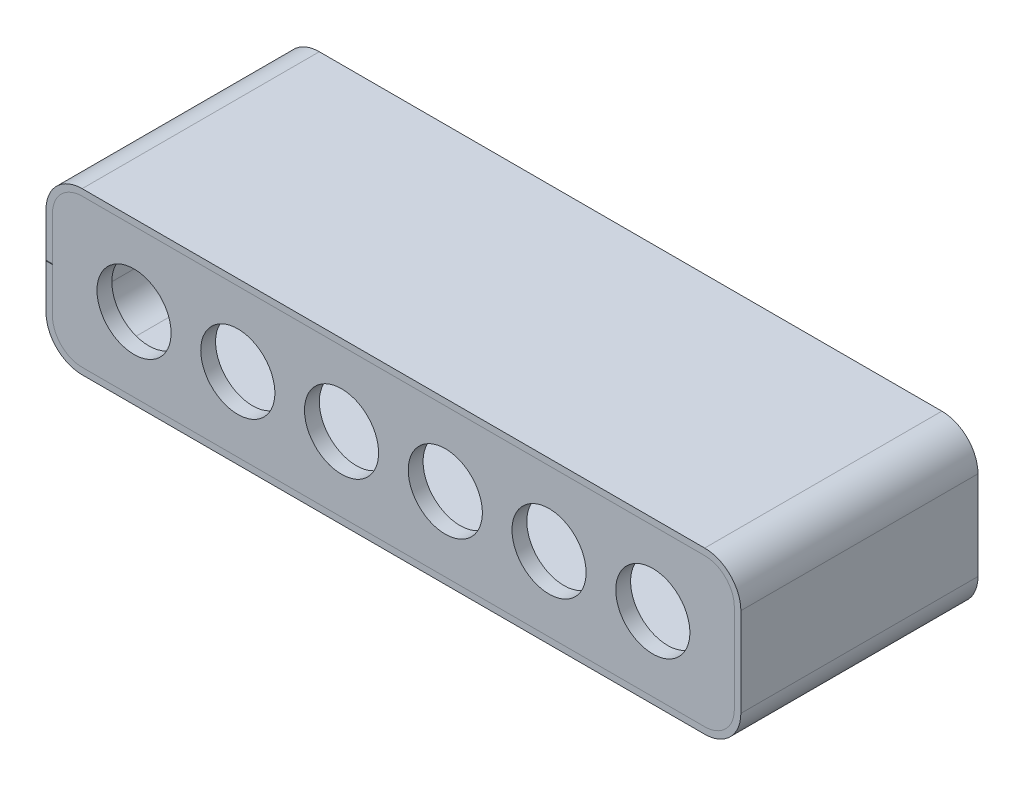
SolidWorks part; units mm, degrees
material "Acrylic (Medium-high impact)"
ref_plane "Front" through (0, 0, 0) normal (0, 0, 1) x (1, 0, 0)
ref_plane "Top" through (0, 0, 0) normal (0, 1, 0) x (1, 0, 0)
ref_plane "Right" through (0, 0, 0) normal (1, 0, 0) x (0, 0, -1)
sketch "Sketch1" plane through (0, 0, 0) normal (0, 0, 1) x (1, 0, 0)
  line L1 (-146.05, 31.75) -> (146.05, 31.75)
  line L2 (-146.05, 31.75) -> (-146.05, -31.75)
  line L3 (-146.05, -31.75) -> (146.05, -31.75)
  line L4 (146.05, 31.75) -> (146.05, -31.75)
  line L5 (-146.05, 31.75) -> (146.05, -31.75) construction
  line L6 (-146.05, -31.75) -> (146.05, 31.75) construction
  point P0 (0, 0)
  dimension "D1" = 292.1
  dimension "D2" = 63.5
extrude "Boss-Extrude1" add sketch "Sketch1" along normal blind 6.35
fillet "Fillet1" radius 12.7 4 edges at (-146.05, -31.75, 3.175) (146.05, -31.75, 3.175) (146.05, 31.75, 3.175) (-146.05, 31.75, 3.175)
sketch "Sketch3" plane through (0, 0, 0) normal (0, 0, 1) x (1, 0, 0)
  line L0 (133.35, 34.544) -> (-133.35, 34.544)
  line L1 (-148.844, 19.05) -> (-148.844, 0.254)
  line L2 (-133.35, -34.544) -> (133.35, -34.544)
  line L3 (148.844, -19.05) -> (148.844, 19.05)
  line L4 (-133.35, -31.75) -> (133.35, -31.75)
  line L5 (-146.05, 19.05) -> (-146.05, -19.05)
  line L6 (133.35, 31.75) -> (-133.35, 31.75)
  line L7 (146.05, -19.05) -> (146.05, 19.05)
  line L8 (-133.35, -31.75) -> (133.35, -31.75)
  line L9 (-146.05, 19.05) -> (-146.05, 0.254)
  line L10 (133.35, 31.75) -> (-133.35, 31.75)
  line L11 (146.05, -19.05) -> (146.05, 19.05)
  line L12 (-146.05, 0) -> (-148.844, 0)
  line L13 (-146.05, 0.254) -> (-148.844, 0.254)
  line L14 (-146.05, 0) -> (-146.05, -19.05)
  line L15 (-146.05, 19.05) -> (-146.05, -19.05) construction
  line L16 (-148.844, 0) -> (-148.844, -19.05)
  line L17 (-148.844, 19.05) -> (-148.844, -19.05) construction
  line L18 (-146.05, 19.05) -> (-146.05, -19.05) construction
  arc A0 (-133.35, 34.544) -> (-148.844, 19.05) centre (-133.35, 19.05) ccw
  arc A1 (-148.844, -19.05) -> (-133.35, -34.544) centre (-133.35, -19.05) ccw
  arc A2 (133.35, -34.544) -> (148.844, -19.05) centre (133.35, -19.05) ccw
  arc A3 (148.844, 19.05) -> (133.35, 34.544) centre (133.35, 19.05) ccw
  arc A4 (-146.05, -19.05) -> (-133.35, -31.75) centre (-133.35, -19.05) ccw
  arc A5 (-133.35, 31.75) -> (-146.05, 19.05) centre (-133.35, 19.05) ccw
  arc A6 (146.05, 19.05) -> (133.35, 31.75) centre (133.35, 19.05) ccw
  arc A7 (133.35, -31.75) -> (146.05, -19.05) centre (133.35, -19.05) ccw
  arc A8 (-146.05, -19.05) -> (-133.35, -31.75) centre (-133.35, -19.05) ccw
  arc A9 (-133.35, 31.75) -> (-146.05, 19.05) centre (-133.35, 19.05) ccw
  arc A10 (146.05, 19.05) -> (133.35, 31.75) centre (133.35, 19.05) ccw
  arc A11 (133.35, -31.75) -> (146.05, -19.05) centre (133.35, -19.05) ccw
  dimension "D3" = 0.254
  dimension "D1" = 0
  dimension "D2" = 2.794
extrude "Boss-Extrude2" add sketch "Sketch3" along normal blind 101.6 separate body
sketch "Sketch4" plane through (0, 0, 101.6) normal (0, 0, 1) x (1, 0, 0)
  line L4 (-146.05, 19.05) -> (-146.05, -19.05)
  line L5 (-133.35, -31.75) -> (133.35, -31.75)
  line L6 (146.05, -19.05) -> (146.05, 19.05)
  line L7 (133.35, 31.75) -> (-133.35, 31.75)
  line L8 (-146.05, 19.05) -> (-146.05, -19.05)
  line L9 (-133.35, -31.75) -> (133.35, -31.75)
  line L10 (146.05, -19.05) -> (146.05, 19.05)
  line L11 (133.35, 31.75) -> (-133.35, 31.75)
  arc A4 (-146.05, -19.05) -> (-133.35, -31.75) centre (-133.35, -19.05) ccw
  arc A5 (133.35, -31.75) -> (146.05, -19.05) centre (133.35, -19.05) ccw
  arc A6 (146.05, 19.05) -> (133.35, 31.75) centre (133.35, 19.05) ccw
  arc A7 (-133.35, 31.75) -> (-146.05, 19.05) centre (-133.35, 19.05) ccw
  arc A8 (-146.05, -19.05) -> (-133.35, -31.75) centre (-133.35, -19.05) ccw
  arc A9 (133.35, -31.75) -> (146.05, -19.05) centre (133.35, -19.05) ccw
  arc A10 (146.05, 19.05) -> (133.35, 31.75) centre (133.35, 19.05) ccw
  arc A11 (-133.35, 31.75) -> (-146.05, 19.05) centre (-133.35, 19.05) ccw
  dimension "D1" = 0
extrude "Boss-Extrude3" add sketch "Sketch4" against normal blind 6.35 separate body
sketch "Sketch2" plane through (0, 0, 0) normal (0, 0, -1) x (-1, 0, 0)
  line L0 (22.225, 0) -> (-22.225, 0) construction
  line L1 (22.225, 0) -> (66.675, 0) construction
  line L2 (66.675, 0) -> (111.125, 0) construction
  line L3 (-22.225, 0) -> (-66.675, 0) construction
  line L4 (-66.675, 0) -> (-111.125, 0) construction
  line L5 (-111.125, 0) -> (-127, 0) construction
  line L6 (111.125, 0) -> (127, 0) construction
  circle A0 centre (-111.125, 0) radius 15.875
  circle A1 centre (-66.675, 0) radius 15.875
  circle A2 centre (-22.225, 0) radius 15.875
  circle A3 centre (22.225, 0) radius 15.875
  circle A4 centre (66.675, 0) radius 15.875
  circle A5 centre (111.125, 0) radius 15.875
  dimension "D1" = 31.75
  dimension "D2" = 254
extrude "Cut-Extrude1" cut sketch "Sketch2" against normal through all
